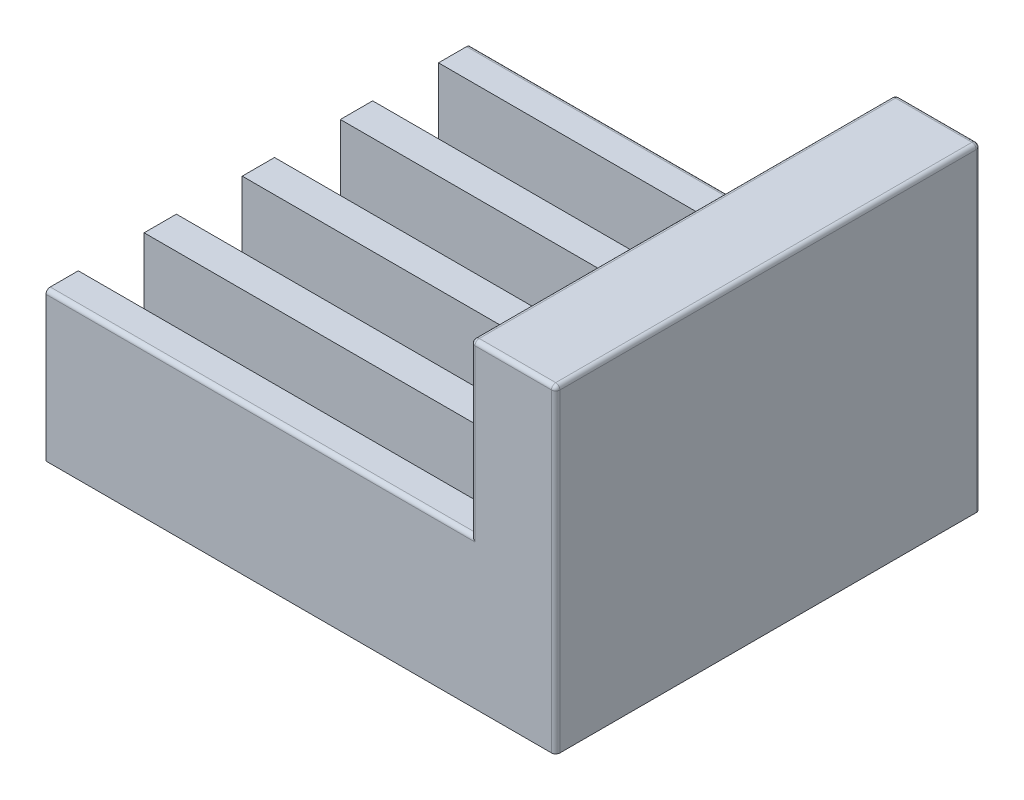
SolidWorks part; units mm, degrees
ref_plane "Front Plane" through (0, 0, 0) normal (0, 0, 1) x (1, 0, 0)
ref_plane "Top Plane" through (0, 0, 0) normal (0, 1, 0) x (1, 0, 0)
ref_plane "Right Plane" through (0, 0, 0) normal (1, 0, 0) x (0, 0, -1)
sketch "Sketch1" plane through (0, 0, 0) normal (0, 1, 0) x (1, 0, 0)
  line L1 (-63.5354, 42.4181) -> (56.4646, 42.4181)
  line L2 (-63.5354, 42.4181) -> (-63.5354, -57.5819)
  line L3 (-63.5354, -57.5819) -> (56.4646, -57.5819)
  line L4 (56.4646, 42.4181) -> (56.4646, -57.5819)
  dimension "D1" = 100
  dimension "D2" = 120
extrude "Boss-Extrude1" add sketch "Sketch1" along normal blind 75
sketch "Sketch2" plane through (0, 75, 0) normal (0, 1, 0) x (1, 0, 0)
  line L0 (-63.5354, -57.5819) -> (56.4646, -57.5819) construction
  line L1 (-63.5354, 42.4181) -> (36.4646, 42.4181)
  line L2 (-63.5354, 42.4181) -> (-63.5354, -57.5819)
  line L3 (-63.5354, -57.5819) -> (36.4646, -57.5819)
  line L4 (36.4646, 42.4181) -> (36.4646, -57.5819)
  dimension "D1" = 100
extrude "Cut-Extrude1" cut sketch "Sketch2" against normal blind 40
sketch "Sketch6" plane through (-63.5354, 0, 0) normal (-1, 0, 0) x (0, 0, 1)
  line L0 (57.5819, 35) -> (-42.4181, 35) construction
  line L1 (-34.8181, 35) -> (-19.3181, 35)
  line L2 (-34.8181, 35) -> (-34.8181, 19.5)
  line L3 (-34.8181, 19.5) -> (-19.3181, 19.5)
  line L4 (-19.3181, 35) -> (-19.3181, 19.5)
  line L5 (-19.3181, 27.25) -> (-11.7181, 27.25) construction
  line L6 (-11.7181, 35) -> (3.7819, 35)
  line L7 (-11.7181, 35) -> (-11.7181, 19.5)
  line L8 (-11.7181, 19.5) -> (3.7819, 19.5)
  line L9 (3.7819, 35) -> (3.7819, 19.5)
  line L10 (11.3819, 35) -> (26.8819, 35)
  line L11 (11.3819, 35) -> (11.3819, 19.5)
  line L12 (11.3819, 19.5) -> (26.8819, 19.5)
  line L13 (26.8819, 35) -> (26.8819, 19.5)
  line L14 (34.4819, 35) -> (49.9819, 35)
  line L15 (34.4819, 35) -> (34.4819, 19.5)
  line L16 (34.4819, 19.5) -> (49.9819, 19.5)
  line L17 (49.9819, 35) -> (49.9819, 19.5)
  line L18 (-15.5181, 27.25) -> (-15.5181, 0) construction
  line L19 (-42.4181, 0) -> (57.5819, 0) construction
  line L20 (7.5819, 35) -> (7.5819, 0) construction
  line L21 (-42.4181, 35) -> (57.5819, 35) construction
  circle A0 centre (-27.0681, 27.25) radius 5.95
  circle A1 centre (-3.9681, 27.25) radius 5.95
  circle A2 centre (42.2319, 27.25) radius 5.95
  circle A3 centre (19.1319, 27.25) radius 5.95
  dimension "D13" = 7.75
  dimension "D1" = 15.5
  dimension "D2" = 15.5
  dimension "D3" = 15.5
  dimension "D4" = 15.5
  dimension "D5" = 15.5
  dimension "D6" = 15.5
  dimension "D7" = 15.5
  dimension "D8" = 15.5
  dimension "D9" = 7.6
  dimension "D10" = 7.6
  dimension "D11" = 7.6
  dimension "D12" = 7.6
  dimension "D14" = 7.75
extrude "Cut-Extrude4" cut sketch "Sketch6" against normal blind 100 contours L11 L10 L13 L12 | L15 L14 L17 L16 | L7 L6 L9 L8 | L2 L1 L4 L3
sketch "Sketch8" plane through (-63.5354, 0, 0) normal (-1, 0, 0) x (0, 0, 1)
  line L1 (-36.6181, 19.5) -> (-17.5181, 19.5)
  line L2 (-36.6181, 19.5) -> (-36.6181, 9.5)
  line L3 (-36.6181, 9.5) -> (-17.5181, 9.5)
  line L4 (-17.5181, 19.5) -> (-17.5181, 9.5)
  line L6 (-15.5181, 35) -> (-15.5181, 0) construction
  line L7 (-19.3181, 35) -> (-11.7181, 35) construction
  line L8 (-42.4181, 0) -> (57.5819, 0) construction
  line L9 (5.5819, 9.5) -> (-13.5181, 9.5)
  line L10 (-13.5181, 19.5) -> (-13.5181, 9.5)
  line L11 (5.5819, 19.5) -> (-13.5181, 19.5)
  line L12 (5.5819, 19.5) -> (5.5819, 9.5)
  line L13 (7.5819, 35) -> (7.5819, 0) construction
  line L14 (11.3819, 35) -> (3.7819, 35) construction
  line L15 (51.7819, 9.5) -> (32.6819, 9.5)
  line L16 (32.6819, 19.5) -> (32.6819, 9.5)
  line L17 (51.7819, 19.5) -> (32.6819, 19.5)
  line L18 (51.7819, 19.5) -> (51.7819, 9.5)
  line L19 (9.5819, 19.5) -> (9.5819, 9.5)
  line L20 (9.5819, 19.5) -> (28.6819, 19.5)
  line L21 (28.6819, 19.5) -> (28.6819, 9.5)
  line L22 (9.5819, 9.5) -> (28.6819, 9.5)
  dimension "D1" = 1.8
  dimension "D2" = 10
  dimension "D3" = 19.1
extrude "Cut-Extrude5" cut sketch "Sketch8" against normal blind 100
extrude "Cut-Extrude6" cut sketch "Sketch6<3>" against normal blind 111 contours A0 | A1 | A3 | A2 region at (-63.5354, 27.25, -27.0681) region at (-63.5354, 27.25, -3.9681) region at (-63.5354, 27.25, 42.2319) region at (-63.5354, 27.25, 19.1319)
sketch "Sketch6<3>" plane through (-63.5354, 0, 0) normal (-1, 0, 0) x (0, 0, 1) same geometry as "Sketch6"
fillet "Fillet1" radius 1 10 edges at (-13.5354, 35, -42.4181) (-13.5354, 35, 57.5819) (36.4646, 55, -42.4181) (36.4646, 55, 57.5819) (46.4646, 75, 57.5819) (36.4646, 75, 7.5819) (46.4646, 75, -42.4181) (56.4646, 75, 7.5819) (56.4646, 37.5, 57.5819) (56.4646, 37.5, -42.4181)
chamfer "Chamfer1" distance 1 angle 45 4 edges at (36.4646, 27.25, 36.2819) (36.4646, 27.25, 13.1819) (36.4646, 27.25, -9.9181) (36.4646, 27.25, -33.0181)
fillet "Fillet2" radius 0.5 4 edges at (47.4646, 27.25, 48.1819) (47.4646, 27.25, 25.0819) (47.4646, 27.25, 1.9819) (47.4646, 27.25, -21.1181)
